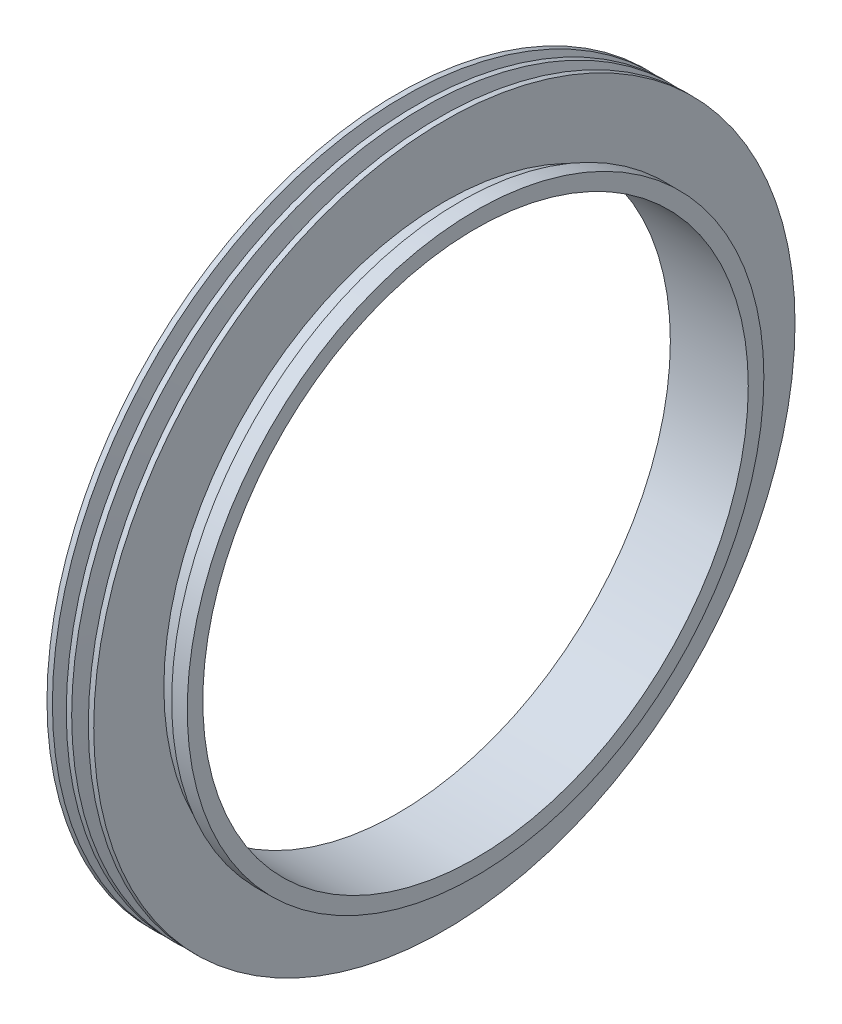
SolidWorks part; units mm, degrees
ref_plane "Płaszczyzna przednia" through (0, 0, 0) normal (0, 0, 1) x (1, 0, 0)
ref_plane "Płaszczyzna górna" through (0, 0, 0) normal (0, 1, 0) x (1, 0, 0)
ref_plane "Płaszczyzna prawa" through (0, 0, 0) normal (1, 0, 0) x (0, 0, -1)
sketch "Szkic1" plane through (0, 0, 0) normal (0, 0, 1) x (1, 0, 0)
  line L0 (0, 17.5) -> (-5, 17.5)
  line L1 (0, 17.5) -> (0, 18.5)
  line L2 (0, 18.5) -> (-1, 18.5)
  line L3 (-1, 18.5) -> (-1, 18)
  line L4 (-1, 18) -> (-2, 18)
  line L5 (-2, 18) -> (-2, 22.5)
  line L6 (-2, 22.5) -> (-2.3474, 22.5)
  line L7 (-2.3474, 22.5) -> (-2.8993, 20.9116)
  line L8 (-2.8993, 20.9116) -> (-3.1016, 20.9116)
  line L9 (-3.1016, 20.9116) -> (-3.4155, 22.5)
  line L10 (-3.4155, 22.5) -> (-3.763, 22.5)
  line L11 (-3.763, 22.5) -> (-4.0817, 20.9116)
  line L12 (-5, 17.5) -> (-5, 22.5)
  line L13 (-5, 22.5) -> (-4.6526, 22.5)
  line L15 (-4.0817, 20.9116) -> (-4.284, 20.9116)
  line L16 (-4.284, 20.9116) -> (-4.6526, 22.5)
  line L17 (0, 0) -> (-5.5314, 0)
  dimension "D1" = 1
  dimension "D2" = 1
  dimension "D3" = 1
  dimension "D4" = 0.5
  dimension "D5" = 4.5
  dimension "D6" = 5
  dimension "D7" = 5
  dimension "D8" = 17.5
revolve "Obrót1" add sketch "Szkic1" angle 360 about L17 region at (-3.2246, 19.5451, 0)
